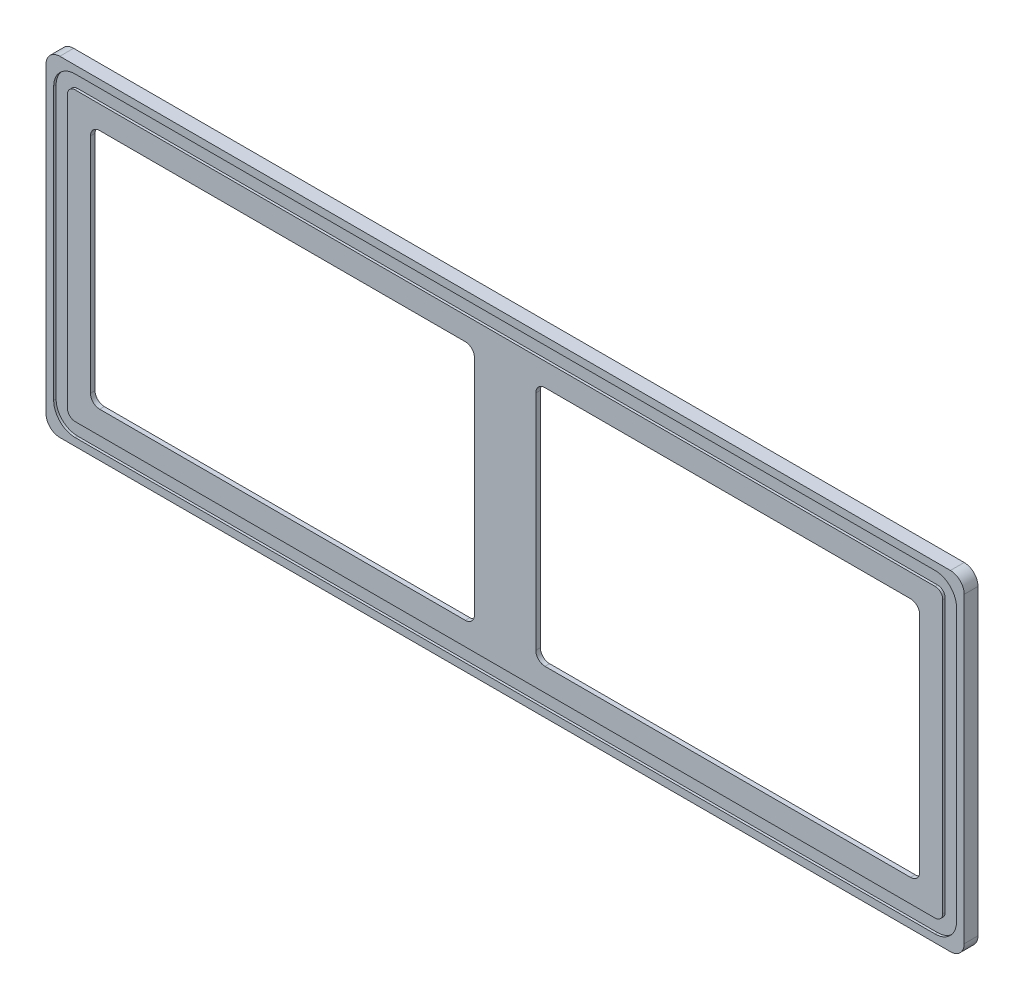
SolidWorks part; units mm, degrees
ref_plane "Front Plane" through (0, 0, 0) normal (0, 0, 1) x (1, 0, 0)
ref_plane "Top Plane" through (0, 0, 0) normal (0, 1, 0) x (1, 0, 0)
ref_plane "Right Plane" through (0, 0, 0) normal (1, 0, 0) x (0, 0, -1)
sketch "Sketch1" plane through (0, 0, 0) normal (0, 0, 1) x (1, 0, 0)
  line L11 (-290.5, 206.4) -> (290.5, 206.4)
  line L12 (299.5, 197.4) -> (299.5, 0)
  line L13 (290.5, -9) -> (-290.5, -9)
  line L14 (-299.5, 197.4) -> (-299.5, 0)
  arc A0 (-290.5, -9) -> (-299.5, 0) centre (-290.5, 0) cw
  arc A1 (290.5, -9) -> (299.5, 0) centre (290.5, 0) ccw
  arc A2 (290.5, 206.4) -> (299.5, 197.4) centre (290.5, 197.4) cw
  arc A3 (-290.5, 206.4) -> (-299.5, 197.4) centre (-290.5, 197.4) ccw
  point P12 (0, -9)
  dimension "D1" = 9
  dimension "D2" = 0
extrude "Boss-Extrude1" add sketch "Sketch1" along normal blind 9
sketch "Sketch4" plane through (0, 0, 9) normal (0, 0, 1) x (1, 0, 0)
  line L0 (290.5, 206.4) -> (-290.5, 206.4) construction
  line L1 (-299.5, 197.4) -> (-299.5, 0) construction
  line L2 (-290.5, -9) -> (290.5, -9) construction
  line L3 (299.5, 0) -> (299.5, 197.4) construction
  line L5 (-280.5, -4) -> (280.5, -4)
  line L6 (-294.5, 10) -> (-294.5, 187.4)
  line L7 (-280.5, 201.4) -> (280.5, 201.4)
  line L8 (294.5, 10) -> (294.5, 187.4)
  line L12 (-280.5, 5) -> (280.5, 5)
  line L13 (285.5, 10) -> (285.5, 187.4)
  line L14 (-280.5, 192.4) -> (280.5, 192.4)
  line L15 (-285.5, 10) -> (-285.5, 187.4)
  line L16 (-294.5, 201.4) -> (294.5, 201.4) construction
  line L17 (294.5, -4) -> (294.5, 201.4) construction
  line L18 (-294.5, -4) -> (294.5, -4) construction
  line L19 (-294.5, -4) -> (-294.5, 201.4) construction
  line L20 (285.5, 5) -> (285.5, 192.4) construction
  line L21 (-285.5, 192.4) -> (285.5, 192.4) construction
  line L22 (-285.5, 5) -> (285.5, 5) construction
  line L23 (-285.5, 5) -> (-285.5, 192.4) construction
  arc A4 (280.5, 201.4) -> (294.5, 187.4) centre (280.5, 187.4) cw
  arc A5 (280.5, -4) -> (294.5, 10) centre (280.5, 10) ccw
  arc A6 (-280.5, -4) -> (-294.5, 10) centre (-280.5, 10) cw
  arc A7 (-294.5, 187.4) -> (-280.5, 201.4) centre (-280.5, 187.4) cw
  arc A8 (285.5, 187.4) -> (280.5, 192.4) centre (280.5, 187.4) ccw
  arc A9 (280.5, 5) -> (285.5, 10) centre (280.5, 10) ccw
  arc A10 (-280.5, 5) -> (-285.5, 10) centre (-280.5, 10) cw
  arc A11 (-280.5, 192.4) -> (-285.5, 187.4) centre (-280.5, 187.4) ccw
  dimension "D6" = 14
  dimension "D7" = 5
  dimension "D1" = 5
  dimension "D2" = 5
  dimension "D3" = 5
  dimension "D4" = 5
  dimension "D5" = 9
extrude "Cut-Extrude1" cut sketch "Sketch4" against normal blind 1.6
sketch "Sketch5" plane through (0, 0, 0) normal (0, 0, 1) x (1, 0, 0)
  line L0 (-285.5, 187.4) -> (-285.5, 10) construction
  line L1 (-264.5, 177.4) -> (-26, 177.4)
  line L2 (-270.5, 171.4) -> (-270.5, 26)
  line L3 (-264.5, 20) -> (-26, 20)
  line L4 (-20, 171.4) -> (-20, 26)
  line L5 (280.5, 192.4) -> (-280.5, 192.4) construction
  line L6 (-280.5, 5) -> (280.5, 5) construction
  line L7 (-290.5, -9) -> (290.5, -9) construction
  arc A0 (-270.5, 26) -> (-264.5, 20) centre (-264.5, 26) ccw
  arc A1 (-26, 20) -> (-20, 26) centre (-26, 26) ccw
  arc A2 (-26, 177.4) -> (-20, 171.4) centre (-26, 171.4) cw
  arc A3 (-264.5, 177.4) -> (-270.5, 171.4) centre (-264.5, 171.4) ccw
  point P20 (0, -9)
  dimension "D4" = 6
  dimension "D1" = 15
  dimension "D2" = 15
  dimension "D3" = 15
  dimension "D5" = 20
extrude "Cut-Extrude2" cut sketch "Sketch5" along normal up to surface (9 mm away) up to face at (0, 98.7, 9)
sketch "Sketch7" plane through (0, 0, 0) normal (0, 0, -1) x (-1, 0, 0)
  line L8 (280.5, 26) -> (280.5, 171.4)
  line L9 (26, 10) -> (264.5, 10)
  line L10 (10, 171.4) -> (10, 26)
  line L11 (264.5, 187.4) -> (26, 187.4)
  line L12 (280.5, 26) -> (280.5, 171.4)
  line L13 (26, 10) -> (264.5, 10)
  line L14 (10, 171.4) -> (10, 26)
  line L15 (264.5, 187.4) -> (26, 187.4)
  arc A8 (264.5, 10) -> (280.5, 26) centre (264.5, 26) ccw
  arc A9 (10, 26) -> (26, 10) centre (26, 26) ccw
  arc A10 (26, 187.4) -> (10, 171.4) centre (26, 171.4) ccw
  arc A11 (280.5, 171.4) -> (264.5, 187.4) centre (264.5, 171.4) ccw
  arc A12 (264.5, 10) -> (280.5, 26) centre (264.5, 26) ccw
  arc A13 (10, 26) -> (26, 10) centre (26, 26) ccw
  arc A14 (26, 187.4) -> (10, 171.4) centre (26, 171.4) ccw
  arc A15 (280.5, 171.4) -> (264.5, 187.4) centre (264.5, 171.4) ccw
  dimension "D1" = 10
extrude "Cut-Extrude4" cut sketch "Sketch7" against normal blind 6
mirror "Mirror1" about plane through (0, 0, 0) normal (1, 0, 0) of "Cut-Extrude4", "Cut-Extrude2"
